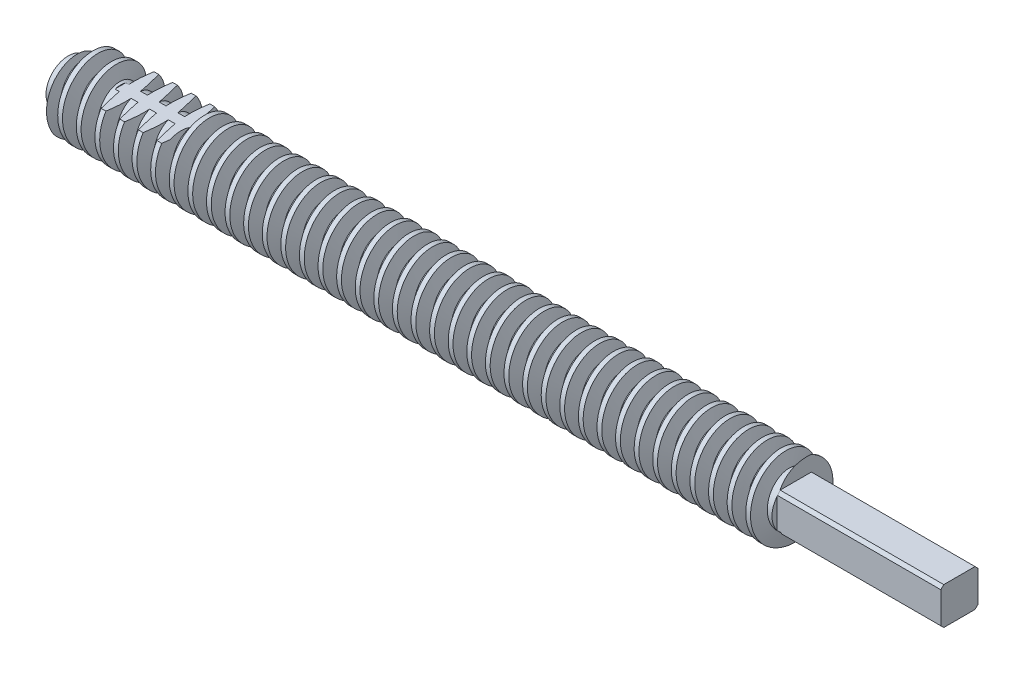
SolidWorks part; units mm, degrees
ref_plane "Front Plane" through (0, 0, 0) normal (0, 0, 1) x (1, 0, 0)
ref_plane "Top Plane" through (0, 0, 0) normal (0, 1, 0) x (1, 0, 0)
ref_plane "Right Plane" through (0, 0, 0) normal (1, 0, 0) x (0, 0, -1)
sketch "Sketch1" plane through (0, 0, 0) normal (0, 0, 1) x (1, 0, 0)
  line L0 (6.35, 0) -> (-97.6665, 0) construction
  line L1 (6.35, 3.175) -> (6.35, 0)
  line L2 (6.35, 3.175) -> (-69.85, 3.175)
  line L3 (-69.85, 3.175) -> (-69.85, 0)
  line L4 (-69.85, 0) -> (6.35, 0)
  dimension "D1" = 6.35
  dimension "D2" = 76.2
  dimension "D3" = 6.35
revolve "Revolve1" add sketch "Sketch1" angle 360 about L0
sketch "Sketch2" plane through (-69.85, 0, 0) normal (-1, 0, 0) x (0, 0, 1)
  circle A0 centre (0, 0) radius 2.6987
  dimension "D1" = 5.3975
curve "Helix/Spiral1" pitch 1.5875 height 63.5 turns 40
sketch "Sketch3" plane through (0, 0, 0) normal (0, 0, 1) x (1, 0, 0)
  line L0 (0, 0) -> (-37.9082, 0) construction
  line L1 (-13.4568, 3.175) -> (-13.1612, 2.032)
  line L2 (6.35, 3.175) -> (-69.85, 3.175) construction
  line L3 (-13.1612, 2.032) -> (-12.5728, 2.032)
  line L4 (-12.867, 2.032) -> (-12.867, 3.175) construction
  line L6 (-13.4568, 3.175) -> (-12.2772, 3.175)
  line L7 (-12.2772, 3.175) -> (-12.5728, 2.032)
  dimension "D1" = 14.5
  dimension "D2" = 6.35
  dimension "D3" = 4.064
  dimension "D4" = 0.2942
sweep "Cut-Sweep1" cut profiles "Sketch3" path "Helix/Spiral1"
sketch "Sketch4" plane through (0, 0, 0) normal (0, 0, 1) x (1, 0, 0)
  line L0 (-71.929, 0.0732) -> (2.5071, 0.0732) construction
  line L1 (-69.215, 1.9782) -> (-69.723, 1.9782)
  line L2 (-69.215, 1.9782) -> (-68.323, 3.5232)
  line L3 (-68.323, 3.5232) -> (-69.85, 3.5232)
  line L4 (-69.723, 1.9782) -> (-69.85, 1.6607)
  line L6 (-69.85, 1.6607) -> (-69.85, 3.5232)
  dimension "D1" = 3.175
revolve "Cut-Revolve1" cut sketch "Sketch4" angle 360 about L0
sketch "Sketch5" plane through (0, 0, 0) normal (0, 0, 1) x (1, 0, 0)
  line L0 (12.7257, 0) -> (-72.8797, 0) construction
  line L1 (6.35, 1.5875) -> (-7.62, 1.5875)
  line L2 (6.35, -3.175) -> (6.35, 3.175) construction
  line L3 (-7.62, 1.5875) -> (-7.62, 4.5095)
  line L4 (-7.62, 4.5095) -> (6.35, 4.5095)
  line L5 (6.35, 4.5095) -> (6.35, 1.5875)
  dimension "D1" = 3.175
  dimension "D2" = 13.97
  dimension "D3" = 2.922
revolve "Cut-Revolve2" [suppressed] cut sketch "Sketch5" angle 360 about L0
sketch "Sketch6" plane through (0, 0, 0) normal (0, 0, 1) x (1, 0, 0)
  line L0 (-69.215, 1.9782) -> (-69.723, 1.9782) construction
  line L1 (-65.278, 1.9782) -> (-59.182, 1.9782)
  line L2 (-65.278, 1.9782) -> (-65.278, 4.0102)
  line L3 (-65.278, 4.0102) -> (-59.182, 4.0102)
  line L4 (-59.182, 1.9782) -> (-59.182, 4.0102)
  line L5 (-65.278, 1.9782) -> (-59.182, 4.0102) construction
  line L6 (-65.278, 4.0102) -> (-59.182, 1.9782) construction
  line L7 (-69.85, 1.6607) -> (-69.85, -1.5143) construction
  point P0 (-62.23, 2.9942)
  dimension "D1" = 0
  dimension "D2" = 2.032
  dimension "D3" = 6.096
  dimension "D4" = 4.572
extrude "Cut-Extrude1" cut sketch "Sketch6" against normal mid plane 12.7
sketch "Sketch7" plane through (6.35, 0, 0) normal (1, 0, 0) x (0, 0, -1)
  line L0 (1.3335, 1.5875) -> (1.5875, 1.3335)
  line L1 (-1.3335, -1.5875) -> (1.3335, -1.5875)
  line L2 (-1.5875, -1.3335) -> (-1.5875, 1.3335)
  line L3 (-1.3335, 1.5875) -> (1.3335, 1.5875)
  line L4 (1.5875, -1.3335) -> (1.5875, 1.3335)
  line L5 (-1.5875, -1.5875) -> (1.5875, 1.5875) construction
  line L6 (-1.5875, 1.5875) -> (1.5875, -1.5875) construction
  line L7 (1.3335, -1.5875) -> (1.5875, -1.3335)
  line L8 (-1.5875, -1.3335) -> (-1.3335, -1.5875)
  line L9 (-1.5875, 1.3335) -> (-1.3335, 1.5875)
  point P0 (0, 0)
  circle M5 centre (0, 0) radius 3.175
  dimension "D1" = 3.175
  dimension "D2" = 3.175
extrude "Cut-Extrude2" cut sketch "Sketch7" against normal blind 13.97 contours L2 L9 L3 L0 L4 L7 L1 L8 M5
